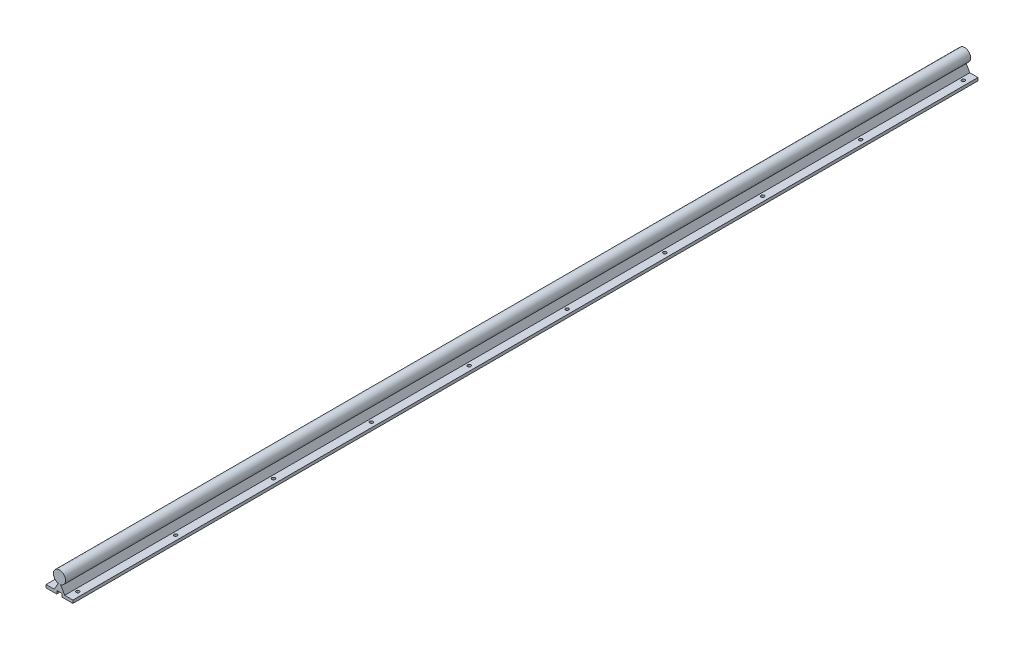
SolidWorks part; units mm, degrees
material "1060 Alloy"
ref_plane "Front Plane" through (0, 0, 0) normal (0, 0, 1) x (1, 0, 0)
ref_plane "Top Plane" through (0, 0, 0) normal (0, 1, 0) x (1, 0, 0)
ref_plane "Right Plane" through (0, 0, 0) normal (1, 0, 0) x (0, 0, -1)
sketch "Sketch1" plane through (0, 0, 0) normal (0, 0, 1) x (1, 0, 0)
  line L0 (-27.5, 0) -> (-4.75, 0)
  line L1 (10.75, 6) -> (2.0897, 21)
  line L2 (-4.75, 0) -> (-4.75, 6.5)
  line L3 (-4.75, 6.5) -> (4.75, 6.5)
  line L4 (-27.5, 0) -> (-27.5, 6)
  line L5 (-27.5, 6) -> (-10.75, 6)
  line L6 (-10.75, 6) -> (-2.0897, 21)
  line L7 (-2.0897, 21) -> (2.0897, 21)
  line L8 (0, 0) -> (0, 50.9475) construction
  line L9 (27.5, 6) -> (10.75, 6)
  line L10 (27.5, 0) -> (27.5, 6)
  line L11 (4.75, 0) -> (4.75, 6.5)
  line L12 (27.5, 0) -> (4.75, 0)
  circle A0 centre (0, 33) radius 12.5
  point P21 (0, 21)
  point P25 (0, 6.5)
  dimension "D1" = 55
  dimension "D5" = 25
  dimension "D2" = 21
  dimension "D3" = 6
  dimension "D4" = 6.5
  dimension "D6" = 21.5
  dimension "D7" = 9.5
  dimension "D8" = 30
  dimension "D9" = 33
extrude "Boss-Extrude1" add sketch "Sketch1" against normal blind 1850 contours L7 L8 A0 L6 | L8 L7 L1 A0 | L8 L3 L11 L12 L10 L9 L1 A0 | L3 L8 A0 L6 L5 L4 L0 L2 | L8 A0 L1 L7 | A0 L8 L7 L6 region at (-27.1558, 3, 0) region at (0.3442, 13.5, 0) region at (-5.3219, 33.0475, 0) region at (-1.0095, 20.7766, 0) region at (1.0095, 20.7766, 0) region at (5.3219, 33.0475, 0)
chamfer "Chamfer1" distance 1 angle 45 2 edges at (-4.75, 0, -925) (4.75, 0, -925)
sketch "Sketch2" plane through (0, 6, 0) normal (0, 1, 0) x (1, 0, 0)
  line L0 (27.5, 0) -> (10.75, 0) construction
  line L1 (0, 0) -> (0, 13.9025) construction
  line L2 (27.5, 1850) -> (10.75, 1850) construction
  line L3 (0, 1850) -> (0, 1839.438) construction
  line L4 (12.5, 1850) -> (-12.5, 1850) construction
  circle A0 centre (17.5, 20) radius 3.3
  circle A1 centre (-17.5, 20) radius 3.3
  circle A2 centre (-17.5, 220) radius 3.3
  circle A3 centre (17.5, 220) radius 3.3
  circle A4 centre (-17.5, 420) radius 3.3
  circle A5 centre (17.5, 420) radius 3.3
  circle A6 centre (-17.5, 620) radius 3.3
  circle A7 centre (17.5, 620) radius 3.3
  circle A8 centre (-17.5, 820) radius 3.3
  circle A9 centre (17.5, 820) radius 3.3
  circle A10 centre (-17.5, 1020) radius 3.3
  circle A11 centre (17.5, 1020) radius 3.3
  circle A12 centre (-17.5, 1220) radius 3.3
  circle A13 centre (17.5, 1220) radius 3.3
  circle A14 centre (-17.5, 1420) radius 3.3
  circle A15 centre (17.5, 1420) radius 3.3
  circle A16 centre (-17.5, 1620) radius 3.3
  circle A17 centre (17.5, 1620) radius 3.3
  circle A20 centre (17.5, 1830) radius 3.3
  circle A21 centre (-17.5, 1830) radius 3.3
  point P53 (0, 1850)
  dimension "D1" = 6.6
  dimension "D6" = 6.6
  dimension "D2" = 20
  dimension "D3" = 35
  dimension "D5" = 200
  dimension "D7" = 20
  dimension "D4" = 9
extrude "Cut-Extrude1" cut sketch "Sketch2" against normal through all both and the other way through all
